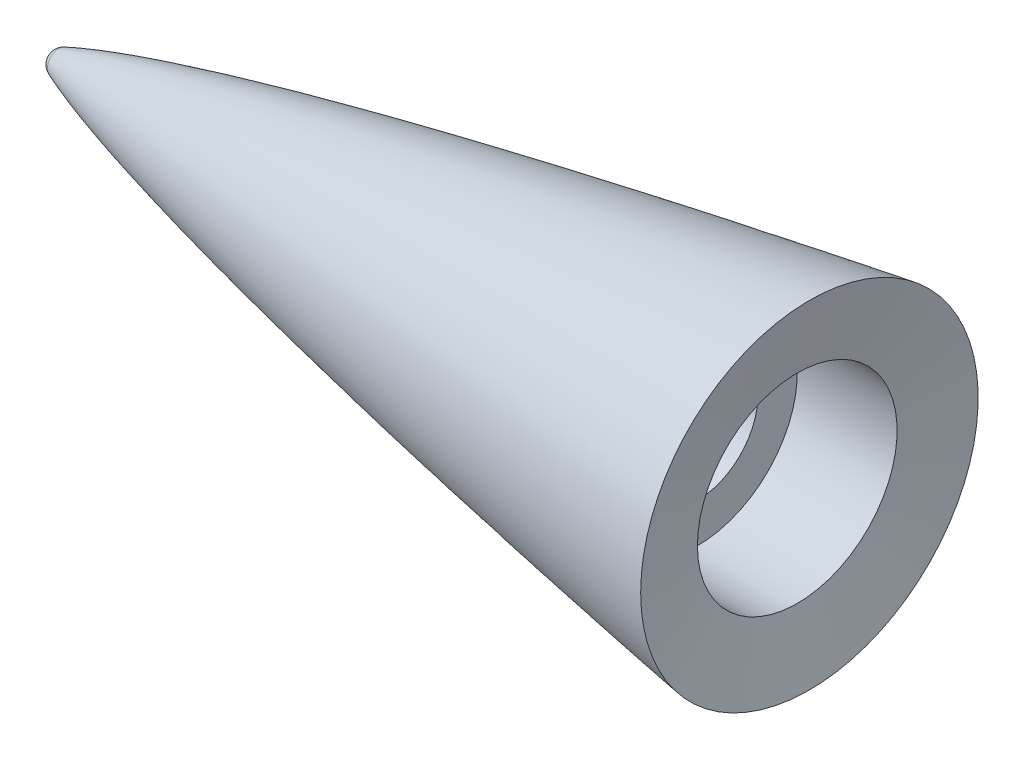
SolidWorks part; units mm, degrees
material "6061-T6 (SS)"
ref_plane "Front Plane" through (0, 0, 0) normal (0, 0, 1) x (1, 0, 0)
ref_plane "Top Plane" through (0, 0, 0) normal (0, 1, 0) x (1, 0, 0)
ref_plane "Right Plane" through (0, 0, 0) normal (1, 0, 0) x (0, 0, -1)
sketch "Sketch1" plane through (0, 0, 0) normal (0, 1, 0) x (1, 0, 0)
  line L0 (0, 0) -> (113.3431, 0) construction
  line L1 (1.6973, 0) -> (45.8194, 0)
  line L2 (83.9194, 12.7) -> (96.6194, 12.7)
  line L3 (96.6194, 12.7) -> (98.1654, 21.4679)
  line L4 (83.9194, 7.6886) -> (58.5194, 7.6886)
  line L5 (83.9194, 12.7) -> (82.8669, 18.9622) construction
  line L6 (58.5194, 7.6886) -> (45.8194, 0)
  line L8 (83.9194, 12.7) -> (83.9194, 7.6886)
  arc A0 (2.6821, 1.4686) -> (1.6973, 0) centre (3.2848, 0) ccw
  spline S0 degree 4 poles (0, 0) (0.0034, 0.0099) (0.0124, 0.0287) (0.036, 0.0594) (0.0734, 0.1004) (0.1241, 0.1478) (0.1961, 0.208) (0.3018, 0.2875) (0.4718, 0.4021) (0.7529, 0.5714) (1.2295, 0.826) (2.0659, 1.2203) (3.5324, 1.8251) (5.9654, 2.7008) (9.9595, 3.9615) (15.3529, 5.459) (21.8477, 7.0868) (29.0559, 8.7493) (36.2876, 10.3139) (43.5327, 11.8013) (50.7947, 13.2272) (58.0593, 14.5995) (64.4352, 15.7629) (69.8852, 16.7323) (74.4605, 17.5301) (78.0669, 18.1509) (81.7865, 18.7815) (85.3087, 19.3727) (89.1704, 20.0106) (92.4601, 20.5499) (97.1008, 21.2989) (100.2743, 21.8052) (104.805, 22.5216) (106.4979, 22.7829) (108.0668, 23.0282) knots 0 0 0 0 0 0.000378 0.000756 0.001385 0.00201 0.00288 0.004147 0.006163 0.009417 0.014733 0.02367 0.039565 0.066726 0.108156 0.174994 0.241832 0.30867 0.375509 0.442347 0.509185 0.576023 0.642862 0.676281 0.7097 0.743119 0.776538 0.809957 0.843376 0.876795 0.910214 0.955107 1 1 1 1 1 construction
  spline S1 degree 4 poles (2.6821, 1.4686) (2.9821, 1.5917) (3.9828, 1.987) (6.0755, 2.7356) (9.9593, 3.9614) (15.3526, 5.4589) (21.8473, 7.0867) (29.0554, 8.7492) (36.2869, 10.3137) (43.5319, 11.8011) (50.7938, 13.227) (58.0582, 14.5993) (64.434, 15.7626) (69.8839, 16.7321) (74.4591, 17.5298) (78.0654, 18.1507) (81.785, 18.7813) (85.3071, 19.3724) (89.1687, 20.0104) (92.4584, 20.5496) (95.6643, 21.067) (97.3334, 21.3349) (98.165, 21.4679) (98.1654, 21.4679) knots 0.027847 0.027847 0.027847 0.027847 0.027847 0.039565 0.066726 0.108156 0.174994 0.241832 0.30867 0.375509 0.442347 0.509185 0.576023 0.642862 0.676281 0.7097 0.743119 0.776538 0.809957 0.843376 0.876795 0.910214 0.910233 0.910233 0.910233 0.910233 0.910233
  dimension "D5" = 7.6886
  dimension "D8" = 100
  dimension "D3" = 12.7
  dimension "D10" = 1.5875
  dimension "D2" = 12.7
  dimension "D4" = 25.4
  dimension "D6" = 12.7
  dimension "D7" = 6.35
revolve "Revolve2" add sketch "Sketch1" angle 360 about L0
